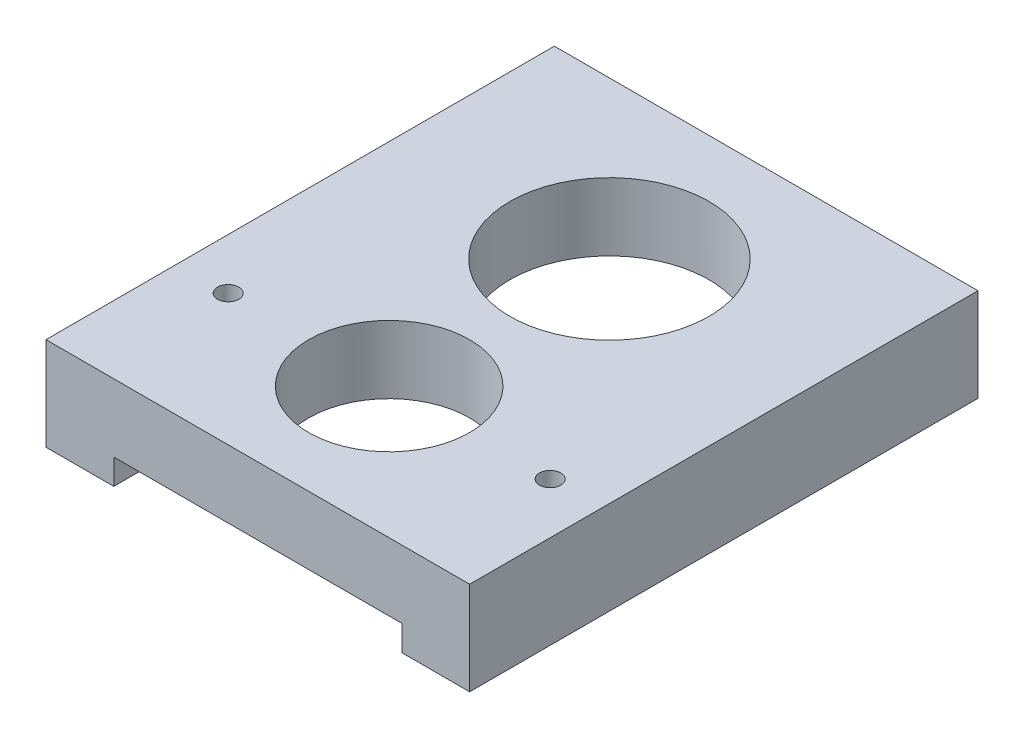
SolidWorks part; units mm, degrees
material "6061 合金"
ref_plane "前基準面" through (0, 0, 0) normal (0, 0, 1) x (1, 0, 0)
ref_plane "上基準面" through (0, 0, 0) normal (0, 1, 0) x (1, 0, 0)
ref_plane "右基準面" through (0, 0, 0) normal (1, 0, 0) x (0, 0, -1)
sketch "草圖1" plane through (0, 0, 0) normal (0, 0, 1) x (1, 0, 0)
  line L0 (-25, 0) -> (-17, 0)
  line L1 (-17, 0) -> (-17, 3)
  line L2 (-17, 3) -> (17, 3)
  line L3 (17, 3) -> (17, 0)
  line L4 (17, 0) -> (25, 0)
  line L5 (25, 0) -> (25, 11)
  line L6 (25, 11) -> (-25, 11)
  line L7 (-25, 11) -> (-25, 0)
  point P3 (0, 3)
  dimension "D1" = 3
  dimension "D2" = 11
  dimension "D3" = 8
  dimension "D4" = 50
extrude "填料-伸長1" add sketch "草圖1" along normal blind 60
sketch "草圖2" plane through (0, 11, 0) normal (0, 1, 0) x (1, 0, 0)
  line L0 (25, 0) -> (-25, 0) construction
  circle A0 centre (0, -18.5) radius 11.75
  point P5 (0, 0)
  dimension "D2" = 23.5
  dimension "D1" = 18.5
extrude "除料-伸長1" cut sketch "草圖2" against normal blind 40
sketch "草圖3" plane through (0, 11, 0) normal (0, 1, 0) x (1, 0, 0)
  line L0 (25, 0) -> (-25, 0) construction
  circle A0 centre (0, -44.5) radius 9.5
  circle A1 centre (0, -18.5) radius 11.75 construction
  point P7 (0, 0)
  dimension "D1" = 26
  dimension "D2" = 19
extrude "除料-伸長2" cut sketch "草圖3" against normal blind 40
hole_wizard "M3x0.5 螺紋孔1" positions "草圖5" profile "草圖6" tap size "M3x0.5" standard "Ansi Metric"
sketch "草圖5" plane through (0, 11, 0) normal (0, 1, 0) x (1, 0, 0)
  line L0 (25, -60) -> (25, 0) construction
  line L1 (25, -60) -> (-25, -60) construction
  line L2 (-25, -60) -> (-25, 0) construction
  point P0 (19, -44.5)
  point P3 (-19, -44.5)
  dimension "D1" = 6
  dimension "D2" = 15.5
  dimension "D3" = 6
  dimension "D4" = 15.5
sketch "草圖6" plane through (19, 11, 44.5) normal (1, 0, 0) x (0, 0, 1)
  line L0 (0, 0) -> (0, 5.7511)
  line L1 (0, 5.7511) -> (1.25, 5)
  line L2 (1.25, 5) -> (1.25, 0)
  line L5 (1.25, 0) -> (0, 0)
  line L10 (0, 5.7511) -> (-1.25, 5) construction
  line L11 (0, -6.35) -> (0, 107.95) construction
  dimension "螺孔鑽直徑" = 2.5
  dimension "螺孔鑽深度" = 5
  dimension "導頭角度" = 118
cosmetic thread "鑽孔螺紋1"
cosmetic thread "鑽孔螺紋2"
